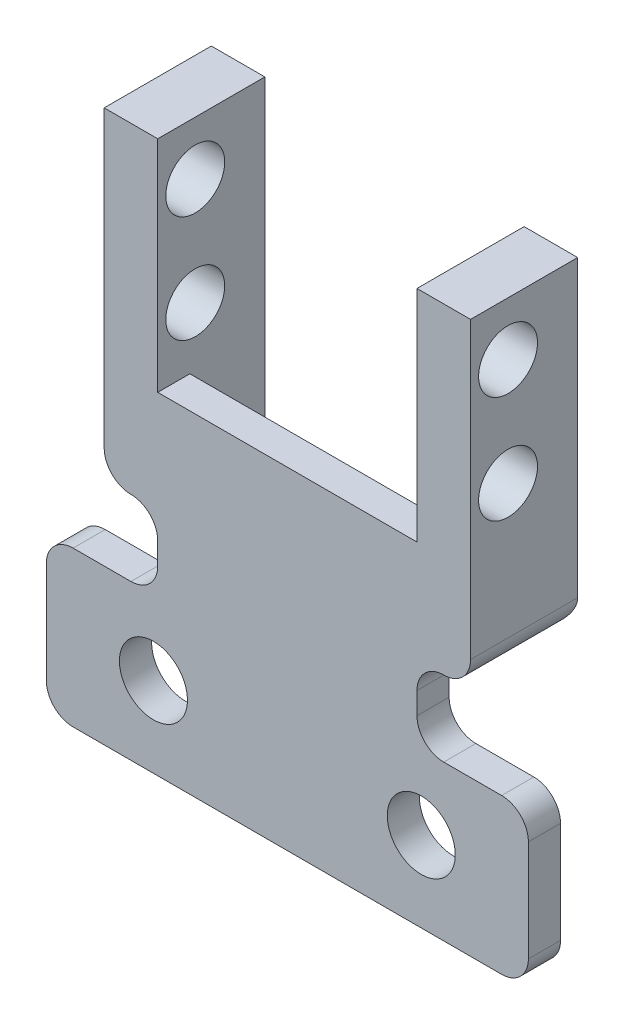
SolidWorks part; units mm, degrees
ref_plane "Front Plane" through (0, 0, 0) normal (0, 0, 1) x (1, 0, 0)
ref_plane "Top Plane" through (0, 0, 0) normal (0, 1, 0) x (1, 0, 0)
ref_plane "Right Plane" through (0, 0, 0) normal (1, 0, 0) x (0, 0, -1)
sketch "Sketch1" plane through (0, 0, 0) normal (0, 0, 1) x (1, 0, 0)
  line L1 (-8.5113, 5.428) -> (36.4887, 5.428)
  line L2 (-8.5113, 5.428) -> (-8.5113, -9.032)
  line L3 (-8.5113, -9.032) -> (36.4887, -9.032)
  line L4 (36.4887, 5.428) -> (36.4887, -9.032)
  dimension "D1" = 45
  dimension "D2" = 14.46
extrude "Boss-Extrude1" add sketch "Sketch1" along normal blind 3
sketch "Sketch2" plane through (0, 0, 0) normal (0, 0, -1) x (-1, 0, 0)
  line L0 (8.5113, -9.032) -> (-36.4887, -9.032) construction
  line L1 (-36.4887, 5.428) -> (8.5113, 5.428) construction
  point P0 (-26.4887, -1.532)
  point P1 (-1.4887, -1.532)
  point P4 (-13.9887, -9.032)
  dimension "D1" = 25
  dimension "D2" = 12.5
  dimension "D3" = 6.96
hole_wizard "1/4 (0.25) Diameter Hole1" positions "Sketch3" profile "Sketch4" hole size "1/4" standard "ANSI Inch" end condition through all
sketch "Sketch3" plane through (0, 0, 0) normal (0, 0, -1) x (-1, 0, 0)
  point P0 (-26.4887, -1.532)
  point P3 (-1.4887, -1.532)
sketch "Sketch4" plane through (26.4887, -1.532, 0) normal (1, 0, 0) x (0, 1, 0)
  line L0 (0, 0) -> (0, 3)
  line L1 (0, 3) -> (3.175, 3)
  line L2 (3.175, 3) -> (3.175, 0)
  line L5 (3.175, 0) -> (0, 0)
  line L11 (0, -6.35) -> (0, 107.95) construction
  dimension "Thru Hole Dia." = 6.35
  dimension "Thru Hole Depth" = 3
sketch "Sketch5" plane through (0, 0, 0) normal (0, 0, -1) x (-1, 0, 0)
  line L0 (-36.4887, 5.428) -> (8.5113, 5.428) construction
  line L1 (-26.0887, 5.428) -> (-1.8887, 5.428)
  line L2 (-26.0887, 5.428) -> (-26.0887, 42.468)
  line L3 (-26.0887, 42.468) -> (-1.8887, 42.468)
  line L4 (-1.8887, 5.428) -> (-1.8887, 42.468)
  line L5 (8.5113, -9.032) -> (-36.4887, -9.032) construction
  point P6 (-13.9887, 42.468)
  point P9 (-13.9887, -9.032)
  dimension "D1" = 24.2
  dimension "D2" = 0
  dimension "D3" = 44
extrude "Boss-Extrude2" add sketch "Sketch5" against normal blind 3
sketch "Sketch6" plane through (1.8887, 0, 0) normal (-1, 0, 0) x (0, 0, 1)
  line L0 (0, 5.428) -> (0, 42.468) construction
  line L1 (3, 42.468) -> (-7, 42.468)
  line L2 (3, 42.468) -> (3, 12.468)
  line L3 (3, 12.468) -> (-7, 12.468)
  line L4 (-7, 42.468) -> (-7, 12.468)
  dimension "D1" = 30
  dimension "D2" = 7
extrude "Boss-Extrude3" add sketch "Sketch6" along normal blind 5
sketch "Sketch7" plane through (-3.1113, 0, 0) normal (-1, 0, 0) x (0, 0, 1)
  line L1 (-7, 42.468) -> (3, 42.468)
  line L2 (-7, 42.468) -> (-7, 12.468)
  line L3 (-7, 12.468) -> (3, 12.468)
  line L4 (3, 42.468) -> (3, 12.468)
extrude "Boss-Extrude4" add sketch "Sketch7" against normal blind 5 from surface starting at face at (26.0887, 23.948, 1.5)
sketch "Sketch8" plane through (-3.1113, 0, 0) normal (-1, 0, 0) x (0, 0, 1)
  line L2 (3, 42.468) -> (-7, 42.468) construction
  line L3 (3, 12.468) -> (3, 42.468) construction
  point P0 (-0.5, 27.468)
  point P1 (-0.5, 37.468)
  dimension "D1" = 3.5
  dimension "D2" = 0
  dimension "D3" = 5
  dimension "D4" = 10
sketch "Sketch12" plane through (0, 0, 0) normal (0, 0, -1) x (-1, 0, 0)
  line L0 (-1.8887, 12.468) -> (-1.8887, 42.468) construction
  line L1 (-26.0887, 42.468) -> (-1.8887, 42.468)
  line L2 (-26.0887, 42.468) -> (-26.0887, 21.968)
  line L3 (-26.0887, 21.968) -> (-1.8887, 21.968)
  line L4 (-1.8887, 42.468) -> (-1.8887, 21.968)
  dimension "D1" = 20.5
extrude "Cut-Extrude1" cut sketch "Sketch12" against normal up to surface (3 mm away) up to face at (23.3137, -1.532, 3)
hole_wizard "M5 Clearance Hole1" positions "Sketch9" profile "Sketch10" hole size "M5" standard "ANSI Metric" end condition through all
sketch "Sketch9" plane through (-3.1113, 0, 0) normal (-1, 0, 0) x (0, 0, 1)
  point P0 (-0.5, 37.468)
  point P3 (-0.5, 27.468)
sketch "Sketch10" plane through (-3.1113, 37.468, -0.5) normal (0, 1, 0) x (0, 0, 1)
  line L0 (0, 0) -> (0, 39.6)
  line L1 (0, 39.6) -> (2.75, 39.6)
  line L2 (2.75, 39.6) -> (2.75, 0)
  line L5 (2.75, 0) -> (0, 0)
  line L11 (0, -6.35) -> (0, 107.95) construction
  dimension "Thru Hole Dia." = 5.5
  dimension "Thru Hole Depth" = 39.6
fillet "Fillet3" radius 2.5 4 edges at (36.4887, -9.032, 1.5) (36.4887, 5.428, 1.5) (-8.5113, -9.032, 1.5) (-8.5113, 5.428, 1.5)
fillet "Fillet4" radius 2.5 8 edges at (1.8887, 5.428, 1.5) (26.0887, 5.428, 1.5) (26.0887, 12.468, 1.5) (1.8887, 12.468, 1.5) (31.0887, 12.468, -2) (-3.1113, 12.468, -2) (28.5887, 12.468, -7) (-0.6113, 12.468, -7)
equation "\"D3@Sketch5\"=15+20 + 9"
